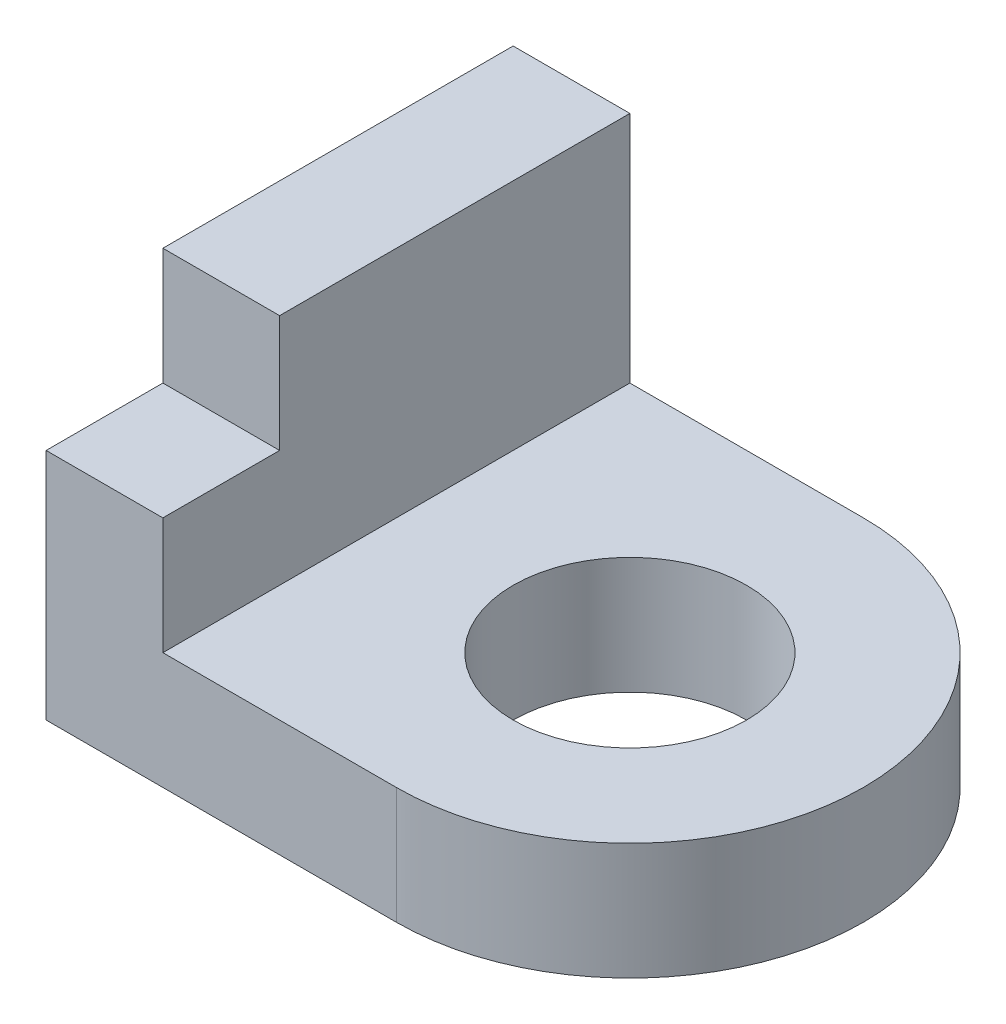
SolidWorks part; units mm, degrees
ref_plane "Front Plane" through (0, 0, 0) normal (0, 0, 1) x (1, 0, 0)
ref_plane "Top Plane" through (0, 0, 0) normal (0, 1, 0) x (1, 0, 0)
ref_plane "Right Plane" through (0, 0, 0) normal (1, 0, 0) x (0, 0, -1)
sketch "Sketch2" plane through (0, 0, 0) normal (0, 1, 0) x (1, 0, 0)
  line L0 (0, 40) -> (0, 0)
  line L1 (0, 0) -> (10, 0)
  line L2 (30, 0) -> (10, 0)
  line L3 (10, 40) -> (10, 0)
  line L4 (10, 10) -> (0, 10)
  line L5 (0, 40) -> (10, 40)
  line L6 (10, 40) -> (30, 40)
  arc A0 (30, 40) -> (30, 0) centre (30, 20) cw
  circle A1 centre (30, 20) radius 10
  point P11 (50, 20)
  dimension "D4" = 20
  dimension "D5" = 50
  dimension "D1" = 10
  dimension "D2" = 40
  dimension "D3" = 10
extrude "Boss-Extrude1" add sketch "Sketch2" along normal blind 30 contours L5 L0 L4 L3 region at (5, 0, -25)
extrude "Boss-Extrude2" add sketch "Sketch2<3>" along normal blind 20 contours L3 L4 L0 L1 region at (5, 0, -5)
sketch "Sketch2<3>" plane through (0, 0, 0) normal (0, 1, 0) x (1, 0, 0) same geometry as "Sketch2"
extrude "Boss-Extrude3" add sketch "Sketch2<4>" along normal blind 10 contours A0 L6 L3 L2 A1 region at (20, 0, -39.4343)
sketch "Sketch2<4>" plane through (0, 0, 0) normal (0, 1, 0) x (1, 0, 0) same geometry as "Sketch2"
